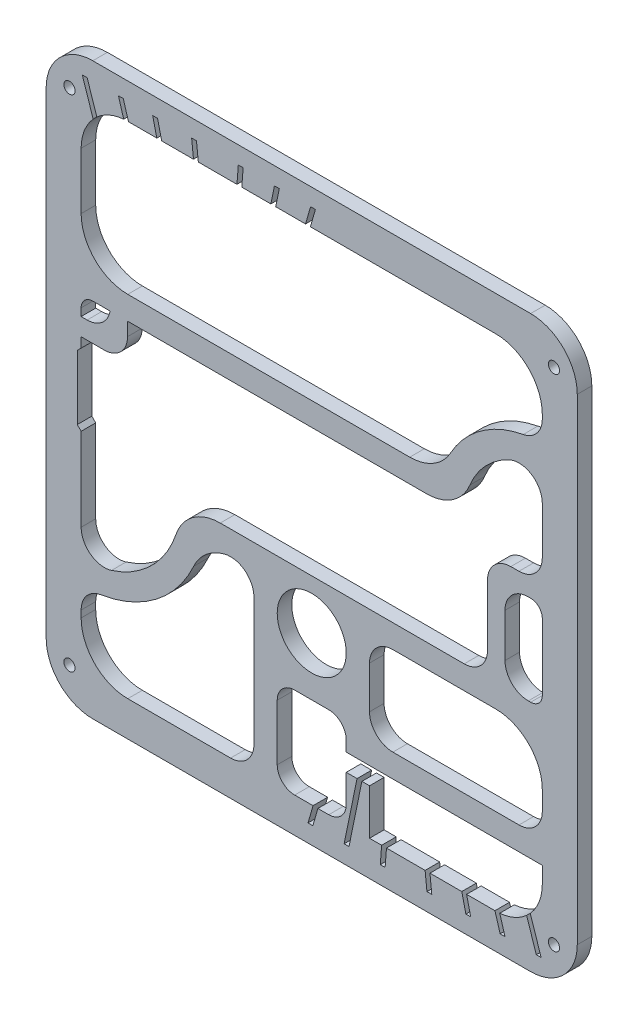
SolidWorks part; units mm, degrees
ref_plane "Front Plane" through (0, 0, 0) normal (0, 0, 1) x (1, 0, 0)
ref_plane "Top Plane" through (0, 0, 0) normal (0, 1, 0) x (1, 0, 0)
ref_plane "Right Plane" through (0, 0, 0) normal (1, 0, 0) x (0, 0, -1)
sketch "Sketch1" plane through (0, 0, 0) normal (0, 0, 1) x (1, 0, 0)
  line L0 (44.642, 23.7892) -> (44.642, 19.9792) construction
  line L1 (-8.1388, 23.7892) -> (49.7286, 23.7892)
  line L2 (-8.1388, 23.7892) -> (-8.1388, -38.311)
  line L3 (-8.1388, -38.311) -> (49.7286, -38.311)
  line L4 (49.7286, 23.7892) -> (49.7286, -38.311)
  line L5 (45.9186, -34.501) -> (-4.3288, -34.501)
  line L6 (45.9186, -34.501) -> (45.9186, 19.9792)
  line L7 (45.9186, 19.9792) -> (-4.3288, 19.9792)
  line L8 (-4.3288, -34.501) -> (-4.3288, 19.9792)
  line L9 (44.642, 21.8842) -> (-35.1587, 21.8842) construction
  line L10 (-4.3288, -31.0517) -> (-8.1388, -31.0517) construction
  line L11 (-6.2338, -31.0517) -> (-6.2338, 6.9585) construction
  line L12 (20.6696, 21.8842) -> (21.1982, 21.8842) construction
  line L13 (-6.2338, -12.887) -> (-6.2338, -25.1298) construction
  line L14 (3.0779, -34.501) -> (3.0779, -38.311) construction
  line L15 (3.0779, -36.406) -> (37.3423, -36.406) construction
  line L17 (49.7286, 15.2205) -> (45.9186, 15.2205) construction
  line L18 (47.8236, 15.2205) -> (47.8236, -0.9437) construction
  line L19 (47.8236, -1.6348) -> (47.8236, 10.608) construction
  line L20 (20.9203, -36.406) -> (20.3916, -36.406) construction
  dimension "D1" = 3.81
  dimension "D2" = 3.81
extrude "Boss-Extrude1" add sketch "Sketch1" along normal blind 1.5875
sketch "Sketch2" plane through (0, 0, 0) normal (0, 0, -1) x (-1, 0, 0)
  line L0 (-45.9186, -34.501) -> (-45.9186, 19.9792) construction
  line L1 (-34.8696, 3.653) -> (4.3288, 3.653)
  line L2 (-45.9186, 3.653) -> (-45.9186, 0.7339)
  line L3 (-37.4096, 1.113) -> (4.3288, 1.113)
  line L4 (4.3288, 3.653) -> (4.3288, 1.113)
  line L5 (4.3288, 19.9792) -> (4.3288, -34.501) construction
  line L6 (-33.4496, 1.113) -> (-36.4496, 1.113) construction
  line L7 (1.2504, -12.887) -> (-36.4496, -12.887) construction
  line L8 (-45.9186, -15.427) -> (-8.8785, -15.427)
  line L9 (-45.9186, -15.427) -> (-45.9186, -12.887)
  line L10 (-45.9186, -12.887) -> (-6.5805, -12.887)
  line L11 (1.357, -21.2563) -> (14.2432, -21.2563) construction
  line L12 (4.3288, -23.7963) -> (4.3288, -26.3363)
  line L13 (-45.9186, 12.162) -> (-45.9186, 9.622)
  arc A0 (-45.9186, 9.622) -> (-37.4096, 1.113) centre (-45.9186, 1.113) cw
  arc A1 (-45.9186, 12.162) -> (-34.8696, 3.653) centre (-45.9186, 0.7339) cw
  arc A2 (4.3288, -23.7963) -> (-6.5805, -12.887) centre (4.3288, -12.887) cw
  arc A3 (-8.8785, -15.427) -> (4.3288, -26.3363) centre (4.3288, -12.887) ccw
  circle A5 centre (1.357, -18.2591) radius 2.9972 construction
  line M5 (-45.9186, -34.501) -> (-45.9186, 19.9792)
  line M7 (4.3288, 19.9792) -> (4.3288, -34.501)
  dimension "D5" = 2.54
  dimension "D1" = 2.54
  dimension "D2" = 2.54
  dimension "D3" = 2.54
  dimension "D4" = 2.54
  dimension "D6" = 2.54
  dimension "D7" = 2.54
extrude "Boss-Extrude2" add sketch "Sketch2" against normal up to surface (1.5875 mm away) contours A1 A0 L3 L1 M5 M7 | L10 L8 M5 M7 region at (15.2704, 3.1385, 0) region at (-3.8086, -25.0663, 0) up to face at (20.7949, -7.2609, 1.5875)
sketch "Sketch3" plane through (0, 0, 0) normal (0, 0, -1) x (-1, 0, 0)
  line L0 (-45.9186, -1.1649) -> (-39.9496, -1.1649)
  line L1 (-45.9186, -12.887) -> (-45.9186, 9.622) construction
  line L2 (-39.9496, -4.387) -> (-39.9496, -11.387) construction
  line L3 (-39.9496, -1.1649) -> (-39.9496, -12.887)
  line L4 (-45.9186, -12.887) -> (-6.5805, -12.887) construction
  line L5 (-39.9496, -12.887) -> (-41.8546, -12.887)
  line L6 (-41.8546, -12.887) -> (-41.8546, -3.0699)
  line L7 (-41.8546, -3.0699) -> (-45.9186, -3.0699)
  line L8 (-45.9186, -3.0699) -> (-45.9186, -1.1649)
  line L9 (-42.9468, 0.7401) -> (-53.4831, 0.7401) construction
  line L10 (-0.7296, 1.113) -> (-0.7296, -2.887)
  line L11 (-37.4096, 1.113) -> (4.3288, 1.113) construction
  line L12 (-1.9996, -2.887) -> (1.2504, -2.887) construction
  line L13 (-0.7296, -2.887) -> (4.3288, -2.887)
  line L14 (4.3288, 1.113) -> (4.3288, -23.7963) construction
  line L15 (4.3288, -2.887) -> (4.3288, -0.982)
  line L16 (4.3288, -0.982) -> (1.1754, -0.982)
  line L17 (1.1754, -0.982) -> (1.1754, 1.113)
  line L18 (1.1754, 1.113) -> (-0.7296, 1.113)
  circle A0 centre (-42.9468, 3.7373) radius 2.9972 construction
  dimension "D1" = 1.905
  dimension "D2" = 1.905
  dimension "D3" = 1.905
  dimension "D4" = 1.905
  dimension "D5" = 1.27
  dimension "D6" = 1.905
extrude "Boss-Extrude3" add sketch "Sketch3" against normal up to surface (1.5875 mm away) up to face at (21.2778, -6.3699, 1.5875)
fillet "Fillet1" radius 5.08 4 edges at (49.7286, -38.311, 0.7937) (-8.1388, -38.311, 0.7937) (-8.1388, 23.7892, 0.7937) (49.7286, 23.7892, 0.7937)
fillet "Fillet2" radius 5.08 10 edges at (8.8785, -15.427, 0.7937) (45.9186, -15.427, 0.7937) (45.9186, -34.501, 0.7937) (-4.3288, -34.501, 0.7937) (34.8696, 3.653, 0.7937) (-4.3288, 3.653, 0.7937) (45.9186, 19.9792, 0.7937) (-4.3288, 19.9792, 0.7937) (6.5805, -12.887, 0.7937) (37.4096, 1.113, 0.7937)
fillet "Fillet3" radius 2.54 11 edges at (41.8546, -3.0699, 0.7938) (39.9496, -12.887, 0.7938) (41.8546, -12.887, 0.7938) (39.9496, -1.1649, 0.7938) (45.9186, -1.1649, 0.7938) (-1.1754, -0.982, 0.7938) (0.7296, -2.887, 0.7938) (45.9186, 9.622, 0.7937) (-4.3288, -26.3363, 0.7937) (-4.3288, -23.7963, 0.7937) (45.9186, 12.162, 0.7937)
fillet "Fillet4" radius 1.27 3 edges at (45.9186, -12.887, 0.7937) (45.9186, -3.0699, 0.7938) (-4.3288, 1.113, 0.7937)
sketch "Sketch5" plane through (0, 0, 0) normal (0, 0, -1) x (-1, 0, 0)
  line L0 (-40.8386, -15.427) -> (-12.5612, -15.427) construction
  line L1 (-27.0941, -15.427) -> (-14.4957, -15.427)
  line L2 (-27.0941, -15.427) -> (-27.0941, -34.501)
  line L3 (-27.0941, -34.501) -> (-14.4957, -34.501)
  line L4 (-14.4957, -15.427) -> (-14.4957, -34.501)
  line L5 (-0.7512, -34.501) -> (-40.8386, -34.501) construction
  line L6 (-24.5541, -18.2972) -> (-27.0941, -18.2972) construction
  line L9 (-17.0357, -18.2972) -> (-14.4957, -18.2972) construction
  circle A1 centre (-20.7949, -18.2972) radius 3.7592 construction
  dimension "D1" = 2.54
extrude "Boss-Extrude4" add sketch "Sketch5" against normal up to surface (1.5875 mm away) up to face at (-3.29, -0.0173, 1.5875)
sketch "Sketch6" plane through (0, 0, 0) normal (0, 0, -1) x (-1, 0, 0)
  circle A0 centre (-20.7949, -18.2972) radius 3.7592 construction
  circle A1 centre (-20.7949, -18.2972) radius 3.7592
extrude "Cut-Extrude2" cut sketch "Sketch6" against normal up to surface (1.5875 mm away) up to face at (4.8008, -25.4732, 1.5875)
sketch "Sketch7" plane through (0, 0, 0) normal (0, 0, -1) x (-1, 0, 0)
  line L0 (-27.0941, -15.427) -> (-27.0941, -34.501) construction
  line L1 (-24.5541, -24.5964) -> (-17.0357, -24.5964)
  line L2 (-24.5541, -24.5964) -> (-24.5541, -34.501)
  line L3 (-24.5541, -34.501) -> (-17.0357, -34.501)
  line L4 (-17.0357, -24.5964) -> (-17.0357, -34.501)
  line L5 (-14.4957, -34.501) -> (-14.4957, -15.427) construction
  line L6 (-0.7512, -34.501) -> (-14.4957, -34.501) construction
  line L7 (-20.7949, -22.0564) -> (-6.5424, -22.0564) construction
  line L8 (-20.7949, -22.0564) -> (-20.7949, -21.3452) construction
  circle A0 centre (-20.7949, -18.2972) radius 3.7592 construction
  dimension "D1" = 2.54
  dimension "D2" = 2.54
  dimension "D3" = 2.54
extrude "Cut-Extrude3" cut sketch "Sketch7" against normal up to surface (1.5875 mm away) up to face at (24.5541, -18.2972, 1.5875)
fillet "Fillet5" radius 1.905 4 edges at (24.5541, -34.501, 0.7937) (17.0357, -34.501, 0.7938) (17.0357, -24.5964, 0.7938) (24.5541, -24.5964, 0.7938)
sketch "Sketch8" plane through (0, 0, 0) normal (0, 0, -1) x (-1, 0, 0)
  line L0 (-45.9186, -29.421) -> (-45.9186, -20.507) construction
  line L1 (-45.9186, -25.103) -> (-27.0941, -25.103)
  line L2 (-45.9186, -25.103) -> (-45.9186, -27.643)
  line L3 (-45.9186, -27.643) -> (-27.0941, -27.643)
  line L4 (-27.0941, -25.103) -> (-27.0941, -27.643)
  line L5 (-27.0941, -15.427) -> (-27.0941, -34.501) construction
  line L6 (-45.7916, -27.643) -> (-20.3916, -27.643) construction
  dimension "D1" = 2.54
extrude "Boss-Extrude5" add sketch "Sketch8" against normal up to surface (1.5875 mm away) up to face at (20.7949, -29.5487, 1.5875)
fillet "Fillet6" radius 2.54 5 edges at (27.0941, -15.427, 0.7937) (14.4957, -15.427, 0.7937) (14.4957, -34.501, 0.7937) (27.0941, -25.103, 0.7937) (45.9186, -25.103, 0.7937)
sketch "Sketch4" plane through (0, 0, 0) normal (0, 0, -1) x (-1, 0, 0)
  line L0 (3.2504, -2.887) -> (4.7504, -4.387) construction
  line L1 (4.7504, -11.387) -> (3.2504, -12.887) construction
  line L2 (3.2504, -2.887) -> (4.7504, -4.387)
  line L3 (4.7504, -11.387) -> (3.2504, -12.887)
  line L4 (4.7504, -4.387) -> (4.7504, -11.387) construction
  line L5 (4.7504, -4.387) -> (4.7504, -11.387)
  line L6 (3.2504, -2.887) -> (3.2504, -12.887)
  line L32 (4.2018, 13.1212) -> (4.2018, 15.0262)
  line L33 (4.2018, 15.0262) -> (1.9364, 15.0262)
  line L34 (1.9364, 15.0262) -> (4.2018, 21.8842)
  line L35 (4.2018, 21.8842) -> (3.6731, 21.8842)
  line L36 (3.6731, 21.8842) -> (1.4078, 15.0262)
  line L37 (1.4078, 15.0262) -> (-1.7768, 15.0262)
  line L38 (-1.7768, 15.0262) -> (0.2648, 21.8842)
  line L39 (0.2648, 21.8842) -> (-0.2639, 21.8842)
  line L40 (-0.2639, 21.8842) -> (-2.3054, 15.0262)
  line L41 (-2.3054, 15.0262) -> (-5.0788, 15.0262)
  line L42 (-5.0788, 15.0262) -> (-3.469, 21.8842)
  line L43 (-3.469, 21.8842) -> (-3.9977, 21.8842)
  line L44 (-3.9977, 21.8842) -> (-5.6074, 15.0262)
  line L45 (-5.6074, 15.0262) -> (-8.4316, 15.0262)
  line L46 (-8.4316, 15.0262) -> (-7.7108, 21.8842)
  line L47 (-7.7108, 21.8842) -> (-8.2395, 21.8842)
  line L48 (-8.2395, 21.8842) -> (-8.9602, 15.0262)
  line L49 (-8.9602, 15.0262) -> (-12.267, 15.0262)
  line L50 (-12.267, 15.0262) -> (-12.7956, 21.8842)
  line L51 (-12.7956, 21.8842) -> (-13.3242, 21.8842)
  line L52 (-13.3242, 21.8842) -> (-12.7956, 15.0262)
  line L53 (-12.7956, 15.0262) -> (-15.3277, 15.0262)
  line L54 (-15.3277, 15.0262) -> (-16.7326, 21.8842)
  line L55 (-16.7326, 21.8842) -> (-17.2612, 21.8842)
  line L56 (-17.2612, 21.8842) -> (-15.8563, 15.0262)
  line L57 (-15.8563, 15.0262) -> (-18.6963, 15.0262)
  line L58 (-18.6963, 15.0262) -> (-20.6696, 21.8842)
  line L59 (-20.6696, 21.8842) -> (-21.1982, 21.8842)
  line L60 (-21.1982, 21.8842) -> (-19.225, 15.0262)
  line L61 (-19.225, 15.0262) -> (-21.1982, 15.0262)
  line L62 (-21.1982, 15.0262) -> (-21.1982, 13.1212)
  line L63 (-21.1982, 13.1212) -> (4.2018, 13.1212)
  line L64 (4.2018, 13.1212) -> (4.2018, 15.0262)
  line L65 (4.2018, 15.0262) -> (1.9364, 15.0262)
  line L66 (1.9364, 15.0262) -> (4.2018, 21.8842)
  line L67 (4.2018, 21.8842) -> (3.6731, 21.8842)
  line L68 (3.6731, 21.8842) -> (1.4078, 15.0262)
  line L69 (1.4078, 15.0262) -> (-1.7768, 15.0262)
  line L70 (-1.7768, 15.0262) -> (0.2648, 21.8842)
  line L71 (0.2648, 21.8842) -> (-0.2639, 21.8842)
  line L72 (-0.2639, 21.8842) -> (-2.3054, 15.0262)
  line L73 (-2.3054, 15.0262) -> (-5.0788, 15.0262)
  line L74 (-5.0788, 15.0262) -> (-3.469, 21.8842)
  line L75 (-3.469, 21.8842) -> (-3.9977, 21.8842)
  line L76 (-3.9977, 21.8842) -> (-5.6074, 15.0262)
  line L77 (-5.6074, 15.0262) -> (-8.4316, 15.0262)
  line L78 (-8.4316, 15.0262) -> (-7.7108, 21.8842)
  line L79 (-7.7108, 21.8842) -> (-8.2395, 21.8842)
  line L80 (-8.2395, 21.8842) -> (-8.9602, 15.0262)
  line L81 (-8.9602, 15.0262) -> (-12.267, 15.0262)
  line L82 (-12.267, 15.0262) -> (-12.7956, 21.8842)
  line L83 (-12.7956, 21.8842) -> (-13.3242, 21.8842)
  line L84 (-13.3242, 21.8842) -> (-12.7956, 15.0262)
  line L85 (-12.7956, 15.0262) -> (-15.3277, 15.0262)
  line L86 (-15.3277, 15.0262) -> (-16.7326, 21.8842)
  line L87 (-16.7326, 21.8842) -> (-17.2612, 21.8842)
  line L88 (-17.2612, 21.8842) -> (-15.8563, 15.0262)
  line L89 (-15.8563, 15.0262) -> (-18.6963, 15.0262)
  line L90 (-18.6963, 15.0262) -> (-20.6696, 21.8842)
  line L91 (-20.6696, 21.8842) -> (-21.1982, 21.8842)
  line L92 (-21.1982, 21.8842) -> (-19.225, 15.0262)
  line L93 (-19.225, 15.0262) -> (-21.1982, 15.0262)
  line L94 (-21.1982, 15.0262) -> (-21.1982, 13.1212)
  line L95 (-21.1982, 13.1212) -> (4.2018, 13.1212)
  line L96 (-45.7916, -27.643) -> (-45.7916, -29.548)
  line L97 (-45.7916, -29.548) -> (-43.5263, -29.548)
  line L98 (-43.5263, -29.548) -> (-45.7916, -36.406)
  line L99 (-45.7916, -36.406) -> (-45.263, -36.406)
  line L100 (-45.263, -36.406) -> (-42.9976, -29.548)
  line L101 (-42.9976, -29.548) -> (-39.8131, -29.548)
  line L102 (-39.8131, -29.548) -> (-41.8546, -36.406)
  line L103 (-41.8546, -36.406) -> (-41.326, -36.406)
  line L104 (-41.326, -36.406) -> (-39.2845, -29.548)
  line L105 (-39.2845, -29.548) -> (-36.5111, -29.548)
  line L106 (-36.5111, -29.548) -> (-38.1208, -36.406)
  line L107 (-38.1208, -36.406) -> (-37.5922, -36.406)
  line L108 (-37.5922, -36.406) -> (-35.9825, -29.548)
  line L109 (-35.9825, -29.548) -> (-33.1583, -29.548)
  line L110 (-33.1583, -29.548) -> (-33.879, -36.406)
  line L111 (-33.879, -36.406) -> (-33.3504, -36.406)
  line L112 (-33.3504, -36.406) -> (-32.6297, -29.548)
  line L113 (-32.6297, -29.548) -> (-29.3229, -29.548)
  line L114 (-29.3229, -29.548) -> (-28.7943, -36.406)
  line L115 (-28.7943, -36.406) -> (-28.2656, -36.406)
  line L116 (-28.2656, -36.406) -> (-28.7943, -29.548)
  line L117 (-28.7943, -29.548) -> (-26.2622, -29.548)
  line L118 (-26.2622, -29.548) -> (-24.8573, -36.406)
  line L119 (-24.8573, -36.406) -> (-24.3286, -36.406)
  line L120 (-24.3286, -36.406) -> (-25.7336, -29.548)
  line L121 (-25.7336, -29.548) -> (-22.8935, -29.548)
  line L122 (-22.8935, -29.548) -> (-20.9203, -36.406)
  line L123 (-20.9203, -36.406) -> (-20.3916, -36.406)
  line L124 (-20.3916, -36.406) -> (-22.3649, -29.548)
  line L125 (-22.3649, -29.548) -> (-20.3916, -29.548)
  line L126 (-20.3916, -29.548) -> (-20.3916, -27.643)
  line L127 (-20.3916, -27.643) -> (-45.7916, -27.643)
  line L128 (-45.7916, -27.643) -> (-45.7916, -29.548)
  line L129 (-45.7916, -29.548) -> (-43.5263, -29.548)
  line L130 (-43.5263, -29.548) -> (-45.7916, -36.406)
  line L131 (-45.7916, -36.406) -> (-45.263, -36.406)
  line L132 (-45.263, -36.406) -> (-42.9976, -29.548)
  line L133 (-42.9976, -29.548) -> (-39.8131, -29.548)
  line L134 (-39.8131, -29.548) -> (-41.8546, -36.406)
  line L135 (-41.8546, -36.406) -> (-41.326, -36.406)
  line L136 (-41.326, -36.406) -> (-39.2845, -29.548)
  line L137 (-39.2845, -29.548) -> (-36.5111, -29.548)
  line L138 (-36.5111, -29.548) -> (-38.1208, -36.406)
  line L139 (-38.1208, -36.406) -> (-37.5922, -36.406)
  line L140 (-37.5922, -36.406) -> (-35.9825, -29.548)
  line L141 (-35.9825, -29.548) -> (-33.1583, -29.548)
  line L142 (-33.1583, -29.548) -> (-33.879, -36.406)
  line L143 (-33.879, -36.406) -> (-33.3504, -36.406)
  line L144 (-33.3504, -36.406) -> (-32.6297, -29.548)
  line L145 (-32.6297, -29.548) -> (-29.3229, -29.548)
  line L146 (-29.3229, -29.548) -> (-28.7943, -36.406)
  line L147 (-28.7943, -36.406) -> (-28.2656, -36.406)
  line L148 (-28.2656, -36.406) -> (-28.7943, -29.548)
  line L149 (-28.7943, -29.548) -> (-26.2622, -29.548)
  line L150 (-26.2622, -29.548) -> (-24.8573, -36.406)
  line L151 (-24.8573, -36.406) -> (-24.3286, -36.406)
  line L152 (-24.3286, -36.406) -> (-25.7336, -29.548)
  line L153 (-25.7336, -29.548) -> (-22.8935, -29.548)
  line L154 (-22.8935, -29.548) -> (-20.9203, -36.406)
  line L155 (-20.9203, -36.406) -> (-20.3916, -36.406)
  line L156 (-20.3916, -36.406) -> (-22.3649, -29.548)
  line L157 (-22.3649, -29.548) -> (-20.3916, -29.548)
  line L158 (-20.3916, -29.548) -> (-20.3916, -27.643)
  line L159 (-20.3916, -27.643) -> (-45.7916, -27.643)
  dimension "D1" = 0
  dimension "D2" = 0
extrude "Cut-Extrude1" cut sketch "Sketch4" against normal up to surface (1.5875 mm away) up to face at (37.5833, -30.9522, 1.5875)
sketch "Sketch9" plane through (0, 0, 0) normal (0, 0, -1) x (-1, 0, 0)
  circle A0 centre (-47.1886, 19.9792) radius 0.6096 construction
  circle A1 centre (5.5988, 19.9792) radius 0.6096 construction
  circle A2 centre (5.5988, -34.501) radius 0.6096 construction
  circle A3 centre (-47.1886, -34.501) radius 0.6096 construction
  circle A4 centre (-47.1886, 19.9792) radius 0.6096
  circle A5 centre (5.5988, 19.9792) radius 0.6096
  circle A6 centre (5.5988, -34.501) radius 0.6096
  circle A7 centre (-47.1886, -34.501) radius 0.6096
extrude "Cut-Extrude4" cut sketch "Sketch9" against normal up to surface (1.5875 mm away) up to face at (18.1234, -5.3808, 1.5875)
